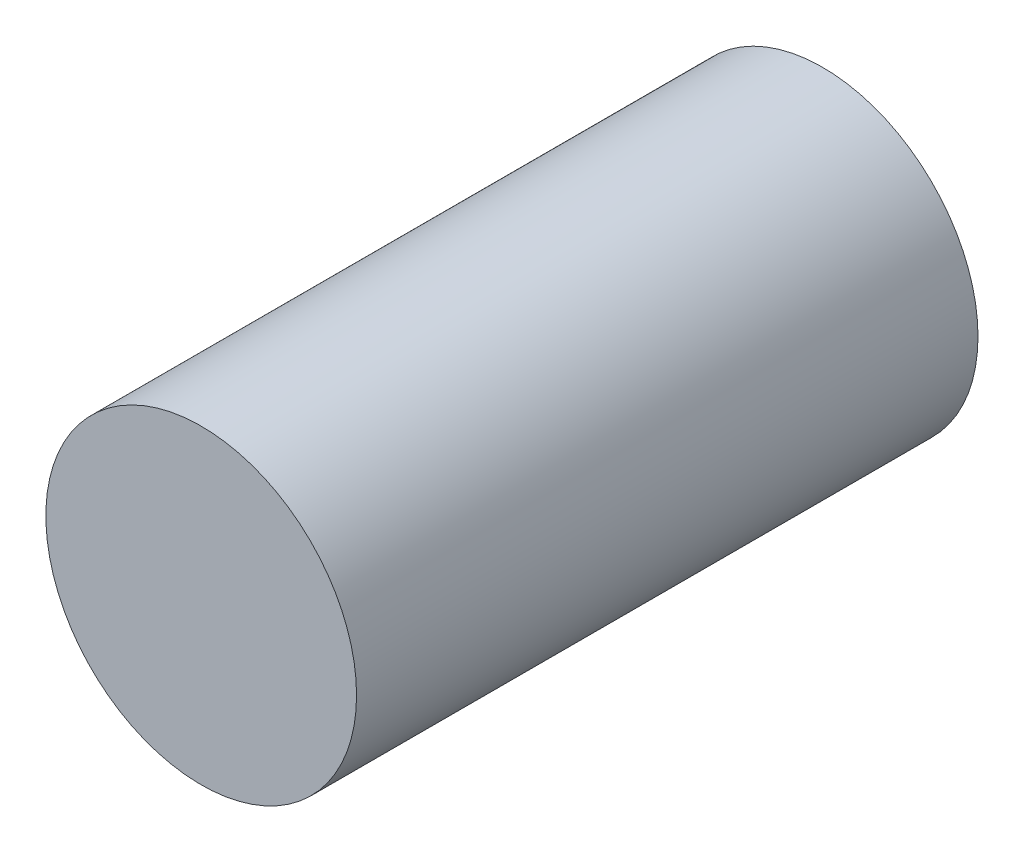
SolidWorks part; units mm, degrees
ref_plane "Front Plane" through (0, 0, 0) normal (0, 0, 1) x (1, 0, 0)
ref_plane "Top Plane" through (0, 0, 0) normal (0, 1, 0) x (1, 0, 0)
ref_plane "Right Plane" through (0, 0, 0) normal (1, 0, 0) x (0, 0, -1)
sketch "Sketch1" plane through (0, 0, 0) normal (0, 0, 1) x (1, 0, 0)
  circle A0 centre (0, 0) radius 0.25
  dimension "D1" = 0.5
extrude "Boss-Extrude1" add sketch "Sketch1" along normal blind 1
